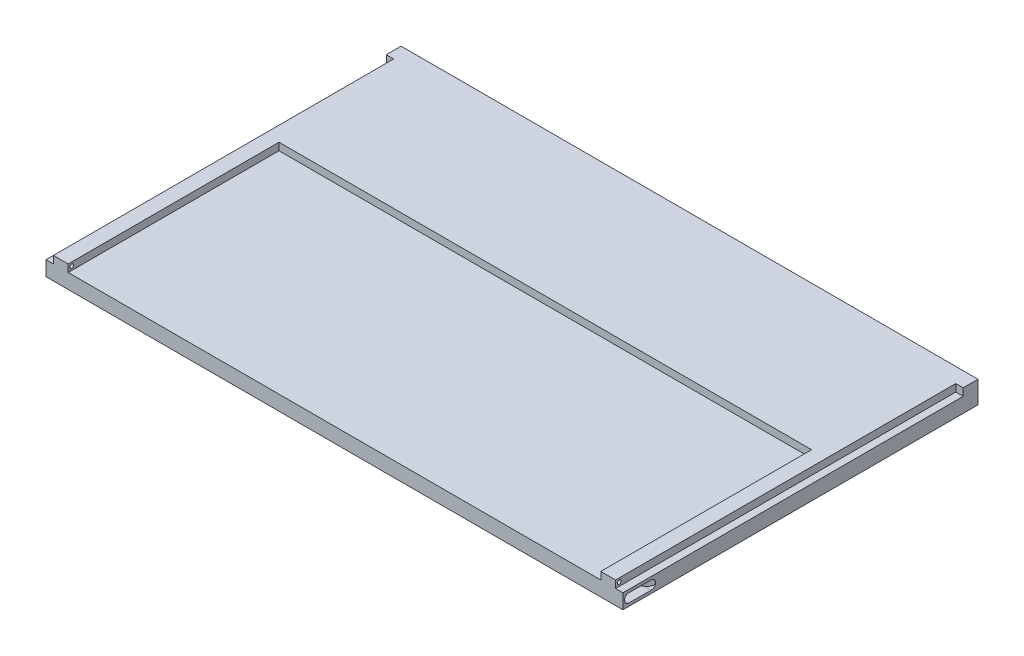
SolidWorks part; units mm, degrees
other "Markup1"
sketch "Sketch12" plane through (250.825, 22.225, 158.75) normal (0.1153, 0.0728, 0.9907) x (0.9687, -0.2289, -0.0959)
material "6061 Alloy"
ref_plane "Front Plane" through (0, 0, 0) normal (0, 0, 1) x (1, 0, 0)
ref_plane "Top Plane" through (0, 0, 0) normal (0, 1, 0) x (1, 0, 0)
ref_plane "Right Plane" through (0, 0, 0) normal (1, 0, 0) x (0, 0, -1)
sketch "Sketch1" plane through (0, 0, 0) normal (0, 1, 0) x (1, 0, 0)
  line L1 (-241.3, 152.4) -> (241.3, 152.4)
  line L2 (-241.3, 152.4) -> (-241.3, -152.4)
  line L3 (-241.3, -152.4) -> (241.3, -152.4)
  line L4 (241.3, 152.4) -> (241.3, -152.4)
  line L5 (-241.3, 152.4) -> (241.3, -152.4) construction
  line L6 (-241.3, -152.4) -> (241.3, 152.4) construction
  point P0 (0, 0)
  dimension "D1" = 482.6
  dimension "D2" = 304.8
extrude "Boss-Extrude1" add sketch "Sketch1" along normal blind 12.7
sketch "Sketch2" plane through (0, 12.7, 0) normal (0, 1, 0) x (1, 0, 0)
  line L0 (-241.3, -152.4) -> (241.3, -152.4) construction
  line L1 (-241.3, 152.4) -> (-228.6, 152.4)
  line L2 (-241.3, 152.4) -> (-241.3, -152.4)
  line L3 (-241.3, -152.4) -> (-228.6, -152.4)
  line L4 (-228.6, 28.575) -> (-228.6, -152.4)
  line L5 (241.3, 152.4) -> (-241.3, 152.4) construction
  line L6 (241.3, 152.4) -> (228.6, 152.4)
  line L7 (241.3, 152.4) -> (241.3, -152.4)
  line L8 (241.3, -152.4) -> (228.6, -152.4)
  line L9 (228.6, 28.575) -> (228.6, -152.4)
  line L10 (-228.6, 152.4) -> (228.6, 152.4)
  line L12 (-228.6, 28.575) -> (228.6, 28.575)
  point P14 (-234.95, -152.4)
  dimension "D1" = 12.7
  dimension "D2" = 180.975
extrude "Boss-Extrude2" add sketch "Sketch2" along normal blind 6.35
sketch "Sketch3" plane through (-241.3, 0, 0) normal (-1, 0, 0) x (0, 0, 1)
  line L0 (152.4, 19.05) -> (152.4, 0) construction
  line L1 (-152.4, 19.05) -> (152.4, 19.05) construction
  circle A0 centre (149.225, 15.875) radius 1.5875
  dimension "D3" = 3.175
  dimension "D1" = 3.175
  dimension "D2" = 3.175
extrude "Cut-Extrude1" cut sketch "Sketch3" against normal through all
sketch "Sketch4" plane through (0, 0, 152.4) normal (0, 0, 1) x (1, 0, 0)
  line L0 (-241.3, 19.05) -> (-241.3, 0) construction
  line L1 (-241.3, 12.7) -> (-247.65, 12.7)
  line L2 (-241.3, 12.7) -> (-241.3, 0)
  line L3 (-241.3, 0) -> (-247.65, 0)
  line L4 (-247.65, 12.7) -> (-247.65, 0)
  line L5 (-241.3, 0) -> (241.3, 0) construction
  dimension "D1" = 12.7
  dimension "D2" = 6.35
extrude "Boss-Extrude3" add sketch "Sketch4" against normal blind 292.1
sketch "Sketch5" plane through (-241.3, 0, 0) normal (-1, 0, 0) x (0, 0, 1)
  line L0 (-152.4, 0) -> (-139.7, 0) construction
  line L1 (-152.4, 19.05) -> (-139.7, 19.05)
  line L2 (-152.4, 19.05) -> (-152.4, 0)
  line L3 (-152.4, 0) -> (-139.7, 0)
  line L4 (-139.7, 19.05) -> (-139.7, 0)
  line L5 (-139.7, 0) -> (-139.7, 12.7) construction
extrude "Boss-Extrude4" add sketch "Sketch5" along normal up to surface (6.35 mm away) up to face at (-247.65, 6.35, 6.35)
mirror "Mirror1" about plane through (0, 0, 0) normal (1, 0, 0) of "Boss-Extrude4", "Boss-Extrude3"
sketch "Sketch6" plane through (-241.3, 0, 0) normal (-1, 0, 0) x (0, 0, 1)
  line L0 (147.32, 6.35) -> (128.27, 6.35) construction
  line L1 (147.32, 2.54) -> (128.27, 2.54)
  line L2 (147.32, 10.16) -> (128.27, 10.16)
  line L3 (152.4, 19.05) -> (152.4, 12.7) construction
  line L5 (152.4, 12.7) -> (152.4, 0) construction
  arc A0 (147.32, 2.54) -> (147.32, 10.16) centre (147.32, 6.35) ccw
  arc A1 (128.27, 10.16) -> (128.27, 2.54) centre (128.27, 6.35) ccw
  point P2 (137.795, 6.35)
  point P11 (152.4, 6.35)
  dimension "D1" = 19.05
  dimension "D2" = 5.08
  dimension "D3" = 7.62
extrude "Cut-Extrude2" cut sketch "Sketch6" against normal blind 25.4 from surface starting at face at (-247.65, 10.5833, -46.5667)
extrude "Cut-Extrude3" cut sketch "Sketch6<2>" along normal blind 25.4 from surface starting at face at (247.65, 10.5833, -46.5667)
sketch "Sketch6<2>" plane through (-241.3, 0, 0) normal (-1, 0, 0) x (0, 0, 1) same geometry as "Sketch6"
sketch "Sketch11" plane through (0, 0, 0) normal (0, -1, 0) x (1, 0, 0)
  line L0 (-247.65, 124.46) -> (-222.25, 124.46)
  line L1 (-222.25, 124.46) -> (-222.25, 140.97)
  line L2 (-222.25, 140.97) -> (-247.65, 124.46)
  line L3 (-222.25, 128.27) -> (-222.25, 147.32) construction
  dimension "D1" = 10.16
extrude "Boss-Extrude5" add sketch "Sketch11" against normal up to surface (10.16 mm away) from surface up to face at (-234.95, 10.16, 137.795) starting at face at (-234.95, 2.54, 137.795)
mirror "Mirror2" about plane through (0, 0, 0) normal (1, 0, 0) of "Boss-Extrude5"
